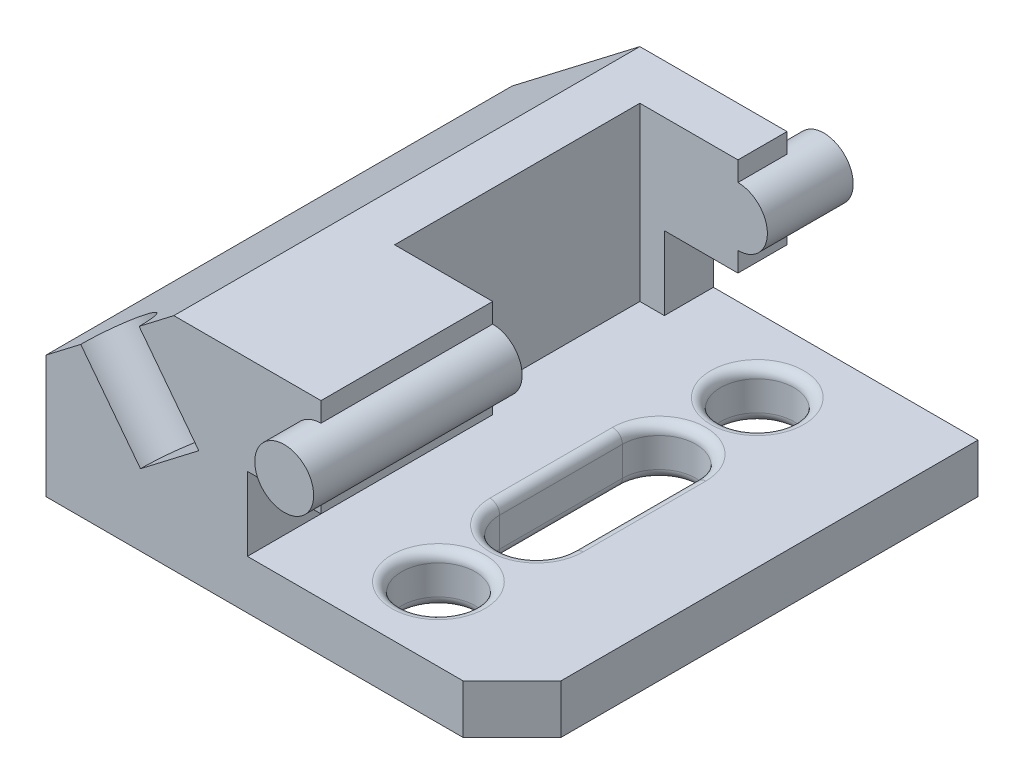
SolidWorks part; units mm, degrees
material "Alliage 1060"
ref_plane "Plan de face" through (0, 0, 0) normal (0, 0, 1) x (1, 0, 0)
ref_plane "Plan de dessus" through (0, 0, 0) normal (0, 1, 0) x (1, 0, 0)
ref_plane "Plan de droite" through (0, 0, 0) normal (1, 0, 0) x (0, 0, -1)
sketch "Esquisse2" plane through (0, 0, 0) normal (0, 0, 1) x (1, 0, 0)
  line L0 (0, 0) -> (0, 25)
  line L1 (0, 25) -> (26.0645, 45)
  line L2 (26.0645, 45) -> (56.0645, 45)
  line L3 (56.0645, 45) -> (56.0645, 25)
  line L4 (56.0645, 25) -> (41.0645, 25)
  line L5 (41.0645, 25) -> (41.0645, 10)
  line L6 (41.0645, 10) -> (95, 10)
  line L7 (95, 10) -> (95, 0)
  line L8 (95, 0) -> (0, 0)
  circle A0 centre (56.0645, 35) radius 6
  dimension "D9" = 12
  dimension "D1" = 25
  dimension "D2" = 20
  dimension "D3" = 30
  dimension "D4" = 20
  dimension "D5" = 15
  dimension "D6" = 10
  dimension "D7" = 95
  dimension "D8" = 52.5
extrude "Boss.-Extru.1" add sketch "Esquisse2" along normal mid plane 95 contours A0 L3 L2 L1 L0 L8 L7 L6 L5 L4 region at (35.4056, 18.0603, 0)
extrude "Boss.-Extru.2" add sketch "Esquisse2<3>" along normal mid plane 110 contours L3 A0 | L3 A0 region at (58.611, 35, 0) region at (53.518, 35, 0)
sketch "Esquisse2<3>" plane through (0, 0, 0) normal (0, 0, 1) x (1, 0, 0) same geometry as "Esquisse2"
sketch "Esquisse3" plane through (-12.0741, 15.7352, 0) normal (-0.6088, 0.7934, 0) x (0.7934, 0.6088, 0)
  line L0 (15.219, -47.5) -> (48.0726, -47.5) construction
  circle A0 centre (31.6458, -47.5) radius 7.5
  dimension "D1" = 15
extrude "Enlèv. mat.-Extru.1" cut sketch "Esquisse3" against normal blind 20 contours A0
sketch "Esquisse4" plane through (0, 45, 0) normal (0, 1, 0) x (1, 0, 0)
  line L0 (26.0645, 47.5) -> (56.0645, 47.5) construction
  line L1 (36.0645, -12.5) -> (78.7544, -12.5)
  line L2 (36.0645, -12.5) -> (36.0645, 37.5)
  line L3 (36.0645, 37.5) -> (78.7544, 37.5)
  line L4 (78.7544, -12.5) -> (78.7544, 37.5)
  line L5 (26.0645, -47.5) -> (26.0645, 47.5) construction
  dimension "D1" = 10
  dimension "D2" = 10
  dimension "D3" = 50
extrude "Enlèv. mat.-Extru.2" cut sketch "Esquisse4" against normal up to surface (35 mm away) up to face at (68.0323, 10, 0)
sketch "Esquisse5" plane through (0, 10, 0) normal (0, 1, 0) x (1, 0, 0)
  line L0 (0, 0) -> (123.7866, 0) construction
  line L1 (41.0645, 47.5) -> (95, 47.5) construction
  line L2 (95, -47.5) -> (95, 47.5) construction
  line L3 (65, -12.5) -> (65, 12.5) construction
  line L6 (41.0645, -47.5) -> (95, -47.5) construction
  line L7 (57.5, -12.5) -> (57.5, 12.5)
  line L8 (72.5, -12.5) -> (72.5, 12.5)
  circle A0 centre (65, 32.5) radius 7.5
  circle A3 centre (65, -32.5) radius 7.5
  arc A4 (57.5, -12.5) -> (72.5, -12.5) centre (65, -12.5) ccw
  arc A5 (72.5, 12.5) -> (57.5, 12.5) centre (65, 12.5) ccw
  point P11 (65, 0)
  point P20 (0, 0)
  point P21 (0, 0)
  dimension "D1" = 15
  dimension "D4" = 7.5
  dimension "D6" = 15
  dimension "D2" = 15
  dimension "D3" = 30
  dimension "D5" = 25
  dimension "D7" = 15
  dimension "D8" = 30
extrude "Enlèv. mat.-Extru.3" cut sketch "Esquisse5" against normal through all
fillet "Congé1" radius 2 12 edges at (65, 0, -20) (72.5, 0, 0) (65, 0, 20) (65, 10, -20) (72.5, 10, 0) (65, 10, 20) (57.5, 10, -32.5) (57.5, 0, -32.5) (57.5, 10, 32.5) (57.5, 0, 32.5) (57.5, 0, 0) (57.5, 10, 0)
chamfer "Chanfrein1" distance 10 angle 45 1 edges at (95, 5, 47.5)
equation "\"A\" = 95"
equation "\"B\" = 50"
equation "\"C\"= 52.5"
equation "\"D7@Esquisse2\"=\"A\""
equation "\"D8@Esquisse2\"=\"C\""
equation "\"D1@Boss.-Extru.1\"=\"A\""
equation "\"D3@Esquisse4\"=\"B\""
